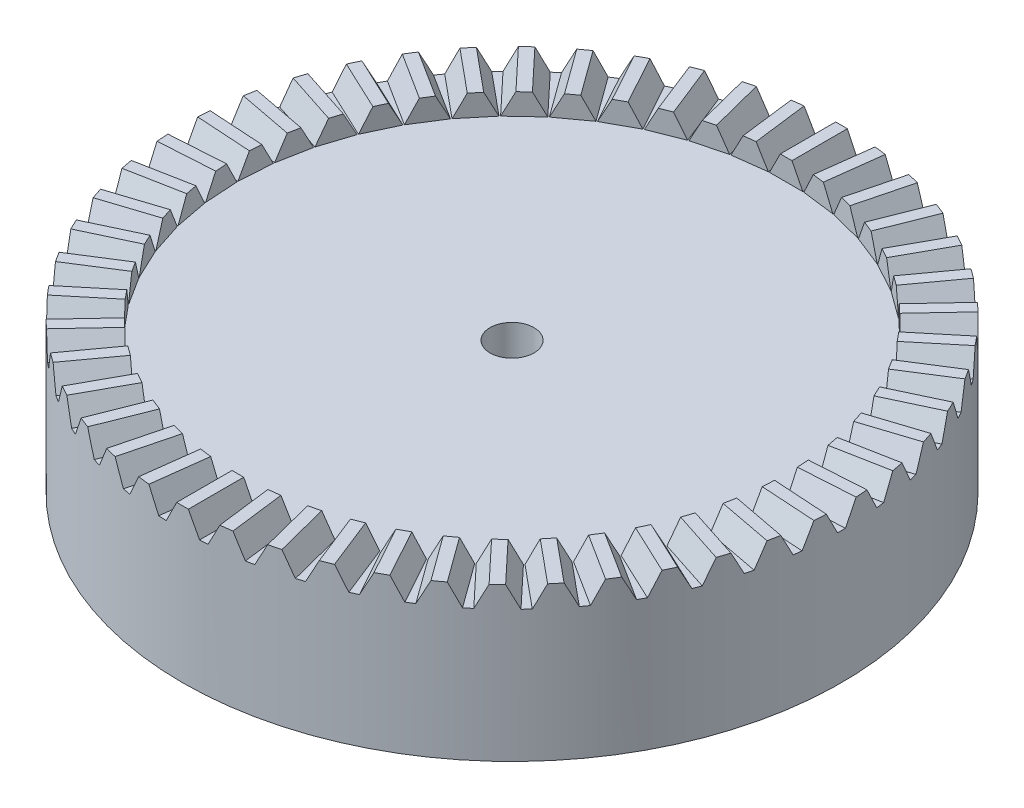
SolidWorks part; units mm, degrees
ref_plane "Front Plane" through (0, 0, 0) normal (0, 0, 1) x (1, 0, 0)
ref_plane "Top Plane" through (0, 0, 0) normal (0, 1, 0) x (1, 0, 0)
ref_plane "Right Plane" through (0, 0, 0) normal (1, 0, 0) x (0, 0, -1)
sketch "Foot Measurements" [suppressed] plane through (0, 0, 0) normal (0, 1, 0) x (1, 0, 0)
  line L0 (0, 0) -> (0, 73) construction
  line L1 (0, 0) -> (0, 147) construction
  line L2 (0, 0) -> (33, 0) construction
  line L3 (0, 0) -> (75, 0) construction
  line L4 (0, 73) -> (33, 73) construction
  line L5 (33, 73) -> (33, 0) construction
  line L6 (0, 147) -> (75, 147) construction
  line L7 (75, 147) -> (75, 0) construction
  line L8 (0, -100) -> (250, -100) construction
  line L9 (0, -100) -> (173, -100) construction
  dimension "D1" = 33
  dimension "D2" = 75
  dimension "D3" = 73
  dimension "D4" = 147
sketch "Sketch3" plane through (0, 0, 0) normal (0, 1, 0) x (1, 0, 0)
  circle A0 centre (0, 0) radius 30
extrude "Boss-Extrude3" add sketch "Sketch3" along normal blind 12
sketch "Sketch6" plane through (0, 12, 0) normal (0, 1, 0) x (1, 0, 0)
  circle A1 centre (0, 0) radius 2
  dimension "D1" = 4
extrude "Cut-Extrude1" cut sketch "Sketch6" against normal up to next
sketch "Sketch5" plane through (0, 12, 0) normal (0, 1, 0) x (1, 0, 0)
  line L3 (-1.5701, 29.9589) -> (-1.5701, 24.9589)
  line L4 (0, 0) -> (-1.5701, 29.9589) construction
  line L5 (0, 0) -> (1.5701, 29.9589) construction
  line L6 (-1.5701, 24.9589) -> (1.5701, 24.9589)
  line L7 (1.5701, 24.9589) -> (1.5701, 29.9589)
  arc A0 (1.5701, 29.9589) -> (-1.5701, 29.9589) centre (0, 0) ccw
  dimension "D2" = 5
  dimension "D1" = 6
  dimension "D3" = 3.1402
extrude "Boss-Extrude5" add sketch "Sketch5" along normal blind 3
sketch "Sketch14" plane through (0, 0, -24.9589) normal (0, 0, 1) x (1, 0, 0)
  line L1 (-1.5701, 12) -> (-1.5701, 15)
  line L2 (-1.5701, 15) -> (1.5701, 15)
  line L3 (1.5701, 12) -> (1.5201, 12)
  line L4 (1.5701, 15) -> (1.5701, 12)
  line L5 (1.5201, 12) -> (0.532, 13.95)
  line L6 (-1.5701, 12) -> (-1.5201, 12)
  line L7 (-1.5201, 12) -> (-0.532, 13.95)
  line L10 (0.532, 13.95) -> (-0.532, 13.95)
  dimension "D1" = 1.05
  dimension "D2" = 0.05
  dimension "D3" = 53.742
  dimension "D4" = 1.0381
extrude "Cut-Extrude4" cut sketch "Sketch14" against normal up to next contours L10 L5 L3 L4 L2 L1 L6 L7 region at (0, 14.0032, -24.9589)
pattern_circular "CirPattern2" count 50 over 360 about axis through (0, -0.001, 0) along (0, 1, 0) of "Cut-Extrude4", "Boss-Extrude5"
